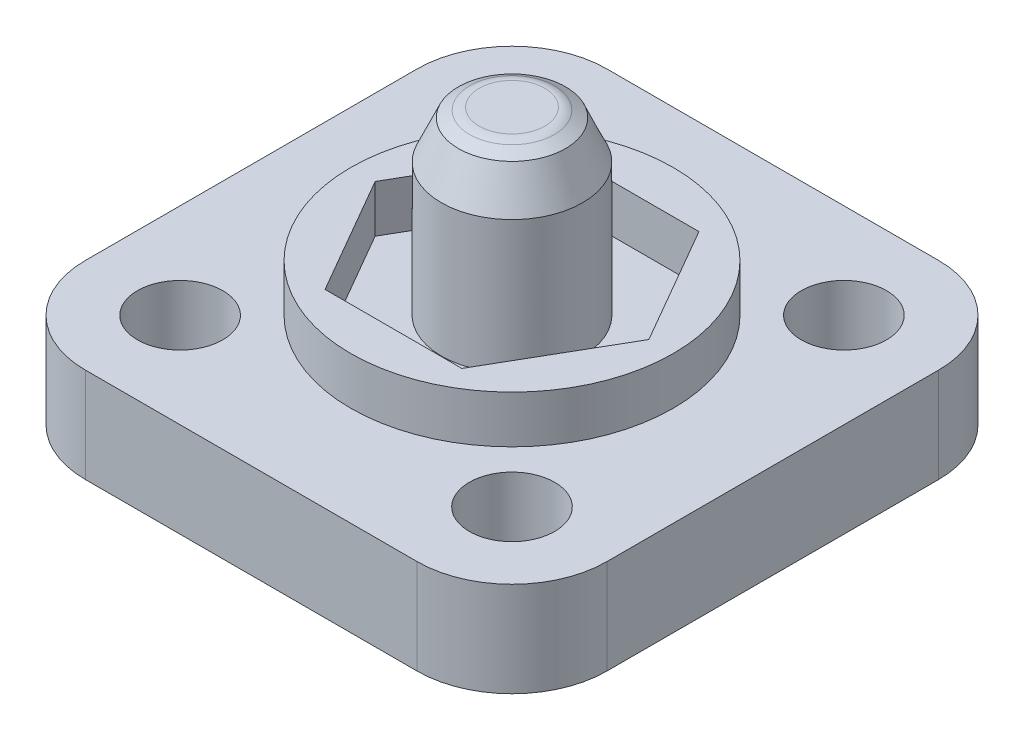
SolidWorks part; units mm, degrees
ref_plane "Front Plane" through (0, 0, 0) normal (0, 0, 1) x (1, 0, 0)
ref_plane "Top Plane" through (0, 0, 0) normal (0, 1, 0) x (1, 0, 0)
ref_plane "Right Plane" through (0, 0, 0) normal (1, 0, 0) x (0, 0, -1)
sketch "Sketch1" plane through (0, 0, 0) normal (0, 0, 1) x (1, 0, 0)
  line L0 (0, 9.5) -> (0, -9.5) construction
  line L1 (0, 9.5) -> (3.4622, 9.5)
  line L2 (4.4653, 9.2303) -> (7.45, 7.5)
  line L3 (7.45, 7.5) -> (7.45, -4.5)
  line L4 (7.45, -9.5) -> (0, -9.5)
  line L5 (0, 9.5) -> (0, -9.5)
  line L6 (7.45, -4.5) -> (17, -4.5)
  line L7 (17, -4.5) -> (17, -9.5)
  line L8 (17, -9.5) -> (7.45, -9.5)
  arc A0 (3.4622, 9.5) -> (4.4653, 9.2303) centre (3.4622, 7.5) cw
  point P4 (0, 0)
  point P10 (4, 9.5)
  dimension "D5" = 2
  dimension "D1" = 17
  dimension "D2" = 2
  dimension "D3" = 14.9
  dimension "D4" = 4
  dimension "D6" = 17
  dimension "D7" = 5
revolve "Revolve1" add sketch "Sketch1" angle 360 about L0
sketch "Sketch2" plane through (0, -9.5, 0) normal (0, -1, 0) x (1, 0, 0)
  line L0 (27.5, 27.5) -> (-27.5, -27.5) construction
  line L1 (17.5, 27.5) -> (-17.5, 27.5)
  line L2 (27.5, 17.5) -> (27.5, -17.5)
  line L3 (17.5, -27.5) -> (-17.5, -27.5)
  line L4 (-27.5, 17.5) -> (-27.5, -17.5)
  arc A0 (-17.5, 27.5) -> (-27.5, 17.5) centre (-17.5, 17.5) ccw
  arc A1 (-17.5, -27.5) -> (-27.5, -17.5) centre (-17.5, -17.5) cw
  arc A2 (27.5, -17.5) -> (17.5, -27.5) centre (17.5, -17.5) cw
  arc A3 (17.5, 27.5) -> (27.5, 17.5) centre (17.5, 17.5) cw
  dimension "D2" = 10
  dimension "D1" = 55
extrude "Boss-Extrude1" add sketch "Sketch2" along normal blind 10
sketch "Sketch3" plane through (0, -9.5, 0) normal (0, 1, 0) x (1, 0, 0)
  circle A0 centre (-17.5, 17.5) radius 4.5
  dimension "D1" = 9
extrude "Cut-Extrude1" cut sketch "Sketch3" against normal through all
mirror "Mirror1" about plane through (0, 0, 0) normal (0, 0, 1) of "Cut-Extrude1" second plane through (0, 0, 0) second plane normal (1, 0, 0)
sketch "Sketch4" plane through (0, -4.5, 0) normal (0, 1, 0) x (1, 0, 0)
  line L1 (14.4338, 0) -> (7.2169, 12.5)
  line L2 (7.2169, 12.5) -> (-7.2169, 12.5)
  line L3 (-7.2169, 12.5) -> (-14.4338, 0)
  line L4 (-14.4338, 0) -> (-7.2169, -12.5)
  line L5 (-7.2169, -12.5) -> (7.2169, -12.5)
  line L6 (7.2169, -12.5) -> (14.4338, 0)
  circle A0 centre (0, 0) radius 12.5 construction
  circle A1 centre (0, 0) radius 7.45 construction
  circle A2 centre (0, 0) radius 7.45
  dimension "D1" = 25
extrude "Cut-Extrude3" cut sketch "Sketch4" against normal blind 5
chamfer "Chamfer1" distance 3 angle 24 1 edges at (0, 7.5, 7.45) first distance on face at (0, 7.5, 7.45)
